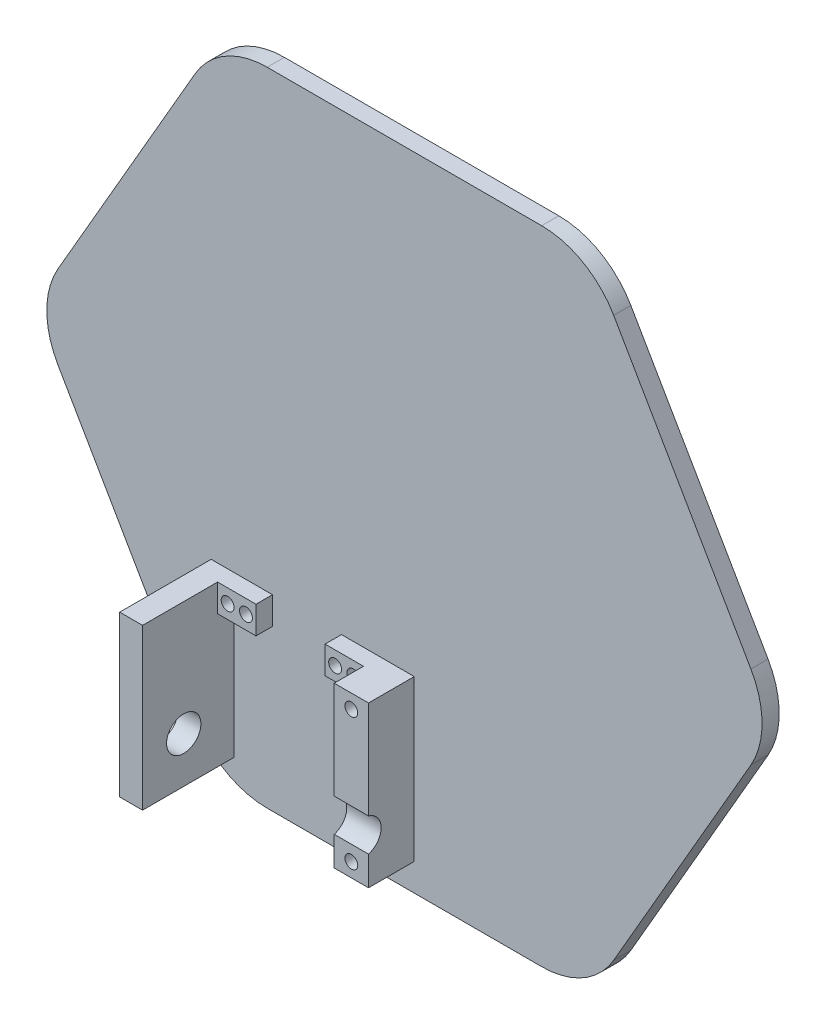
SolidWorks part; units mm, degrees
ref_plane "Front Plane" through (0, 0, 0) normal (0, 0, 1) x (1, 0, 0)
ref_plane "Top Plane" through (0, 0, 0) normal (0, 1, 0) x (1, 0, 0)
ref_plane "Right Plane" through (0, 0, 0) normal (1, 0, 0) x (0, 0, -1)
sketch "Sketch2" plane through (0, 0, 0) normal (0, 0, 1) x (1, 0, 0)
  line L1 (96.2019, 11.5481) -> (58.1019, 77.5392)
  line L2 (38.1, 89.0873) -> (-38.1, 89.0873)
  line L3 (-58.1019, 77.5392) -> (-96.2019, 11.5481)
  line L4 (-96.2019, -11.5481) -> (-58.1019, -77.5392)
  line L5 (-38.1, -89.0873) -> (38.1, -89.0873)
  line L6 (58.1019, -77.5392) -> (96.2019, -11.5481)
  circle A0 centre (0, 0) radius 89.0873 construction
  arc A1 (58.1019, 77.5392) -> (38.1, 89.0873) centre (38.1, 65.9911) ccw
  arc A2 (96.2019, 11.5481) -> (96.2019, -11.5481) centre (76.2, 0) cw
  arc A3 (38.1, -89.0873) -> (58.1019, -77.5392) centre (38.1, -65.9911) ccw
  arc A4 (-58.1019, -77.5392) -> (-38.1, -89.0873) centre (-38.1, -65.9911) ccw
  arc A5 (-96.2019, 11.5481) -> (-96.2019, -11.5481) centre (-76.2, 0) ccw
  arc A6 (-38.1, 89.0873) -> (-58.1019, 77.5392) centre (-38.1, 65.9911) ccw
  dimension "D1" = 76.2
extrude "Boss-Extrude1" add sketch "Sketch2" along normal blind 4.7625
sketch "Sketch4" plane through (0, 0, 4.7625) normal (0, 0, 1) x (1, 0, 0)
  line L0 (-38.1, -89.0873) -> (38.1, -89.0873) construction
  line L1 (-53.6569, -81.4673) -> (-47.3069, -81.4673)
  line L2 (-53.6569, -81.4673) -> (-53.6569, -37.0173)
  line L3 (-53.6569, -37.0173) -> (-47.3069, -37.0173)
  line L4 (-47.3069, -81.4673) -> (-47.3069, -37.0173)
  point P17 (0, 0)
  dimension "D1" = 6.35
  dimension "D2" = 44.45
  dimension "D3" = 7.62
  dimension "D4" = 4.445
extrude "Boss-Extrude3" add sketch "Sketch4" along normal blind 25.4
sketch "Sketch5" plane through (0, 0, 4.7625) normal (0, 0, 1) x (1, 0, 0)
  line L1 (-6.7975, -81.4673) -> (2.7275, -81.4673)
  line L2 (-6.7975, -81.4673) -> (-6.7975, -37.0173)
  line L3 (-6.7975, -37.0173) -> (2.7275, -37.0173)
  line L4 (2.7275, -81.4673) -> (2.7275, -37.0173)
  line L6 (-53.6569, -81.4673) -> (-47.3069, -81.4673) construction
  point P19 (0, 0)
  dimension "D1" = 9.525
extrude "Boss-Extrude6" add sketch "Sketch5" along normal blind 12.7
sketch "Sketch6" plane through (0, 0, 4.7625) normal (0, 0, 1) x (1, 0, 0)
  line L0 (-17.4655, -37.0173) -> (-6.7975, -37.0173)
  line L1 (-47.3069, -37.0173) -> (-36.6389, -37.0173)
  line L2 (-47.3069, -37.0173) -> (-47.3069, -44.6373)
  line L3 (-47.3069, -44.6373) -> (-36.6389, -44.6373)
  line L4 (-36.6389, -37.0173) -> (-36.6389, -44.6373)
  line L5 (-17.4655, -37.0173) -> (-17.4655, -44.6373)
  line L6 (-17.4655, -44.6373) -> (-6.7975, -44.6373)
  line L7 (-6.7975, -37.0173) -> (-6.7975, -44.6373)
  line L8 (-6.7975, -37.0173) -> (-6.7975, -81.4673) construction
  line L9 (2.7275, -37.0173) -> (-6.7975, -37.0173) construction
  line L11 (-47.3069, -81.4673) -> (-47.3069, -37.0173) construction
  point P16 (0, 0)
  dimension "D1" = 7.62
  dimension "D2" = 10.668
  dimension "D3" = 7.62
  dimension "D4" = 10.668
extrude "Boss-Extrude5" add sketch "Sketch6" along normal blind 4.572
sketch "Sketch7" plane through (0, 0, 9.3345) normal (0, 0, 1) x (1, 0, 0)
  line L0 (-47.3069, -44.6373) -> (-36.6389, -44.6373) construction
  line L1 (-36.6389, -44.6373) -> (-36.6389, -37.0173) construction
  line L2 (-17.4655, -44.6373) -> (-6.7975, -44.6373) construction
  line L3 (-17.4655, -37.0173) -> (-17.4655, -44.6373) construction
  circle A0 centre (-44.5129, -40.8273) radius 1.7907
  circle A1 centre (-39.4329, -40.8273) radius 1.7907
  circle A2 centre (-14.6715, -40.8273) radius 1.7907
  circle A3 centre (-9.5915, -40.8273) radius 1.7907
  dimension "D1" = 3.5814
  dimension "D2" = 3.81
  dimension "D8" = 3.5814
  dimension "D9" = 3.5814
  dimension "D10" = 3.5814
  dimension "D3" = 5.08
  dimension "D4" = 2.794
  dimension "D5" = 3.81
  dimension "D6" = 2.794
  dimension "D7" = 5.08
extrude "Cut-Extrude1" cut sketch "Sketch7" against normal blind 6.731
sketch "Sketch9" plane through (-53.6569, 0, 0) normal (-1, 0, 0) x (0, 0, 1)
  line L0 (4.7625, -37.0173) -> (4.7625, -81.4673) construction
  line L1 (30.1625, -81.4673) -> (4.7625, -81.4673) construction
  circle A0 centre (7.5311, -68.7673) radius 2.286
  dimension "D1" = 4.572
  dimension "D2" = 2.7686
  dimension "D3" = 12.7
sketch "Sketch10" plane through (-53.6569, 0, 0) normal (-1, 0, 0) x (0, 0, 1)
  line L0 (30.1625, -81.4673) -> (4.7625, -81.4673) construction
  circle A0 centre (18.7325, -68.7673) radius 4.7625
  dimension "D1" = 9.525
  dimension "D2" = 11.2014
  dimension "D3" = 12.7
extrude "Cut-Extrude3" cut sketch "Sketch9" against normal blind 2.54
extrude "Cut-Extrude4" cut sketch "Sketch10" against normal up to surface (6.35 mm away) up to face at (-47.3069, -54.374, 14.7532)
sketch3d "3DSketch1"
  line L0 (0, 0, 0) -> (0, 0, 50000) construction
sketch "Sketch11" plane through (-6.7975, 0, 0) normal (-1, 0, 0) x (0, 0, 1)
  circle A0 centre (18.7325, -68.7673) radius 4.7625 construction
  circle A1 centre (18.7325, -68.7673) radius 4.7625 construction
  circle A2 centre (18.7325, -68.7673) radius 4.7625
  dimension "D1" = 9.525
extrude "Cut-Extrude5" cut sketch "Sketch11" against normal through all
sketch "Sketch12" plane through (0, 0, 17.4625) normal (0, 0, 1) x (1, 0, 0)
  line L0 (2.7275, -64.1773) -> (2.7275, -37.0173) construction
  line L2 (-6.7975, -81.4673) -> (2.7275, -81.4673) construction
  line L3 (2.7275, -37.0173) -> (-6.7975, -37.0173) construction
  circle A0 centre (-2.035, -40.9162) radius 1.778
  circle A1 centre (-2.035, -77.5684) radius 1.778
  dimension "D1" = 3.556
  dimension "D4" = 3.556
  dimension "D2" = 4.7625
  dimension "D3" = 3.8989
  dimension "D5" = 3.8989
extrude "Cut-Extrude6" cut sketch "Sketch12" against normal blind 6.731
